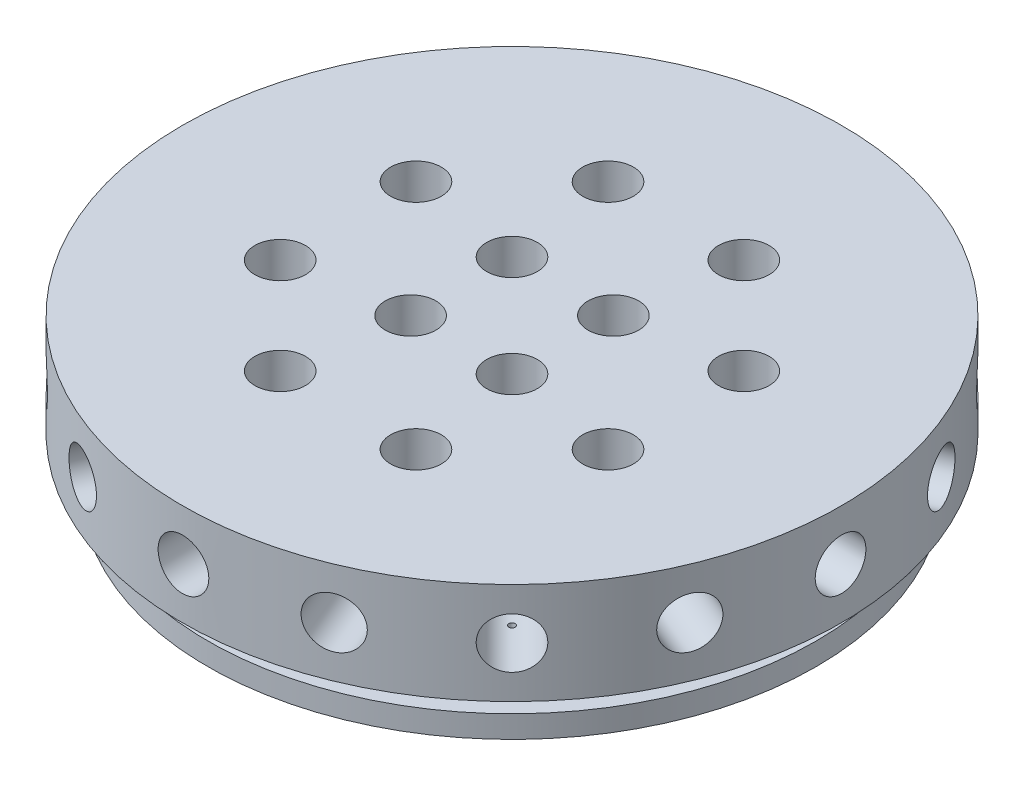
SolidWorks part; units mm, degrees
ref_plane "Front Plane" through (0, 0, 0) normal (0, 0, 1) x (1, 0, 0)
ref_plane "Top Plane" through (0, 0, 0) normal (0, 1, 0) x (1, 0, 0)
ref_plane "Right Plane" through (0, 0, 0) normal (1, 0, 0) x (0, 0, -1)
ref_axis "Axis1" through (0, -42.3, 0) along (0, 1, 0)
sketch "Sketch1" plane through (0, 0, 0) normal (0, 0, 1) x (1, 0, 0)
  line L0 (0, 0) -> (-38.1, 0)
  line L1 (-38.1, 0) -> (-38.1, 2.7877)
  line L2 (-38.1, 2.7877) -> (-36.068, 2.7877)
  line L3 (-36.068, 2.7877) -> (-36.068, 5.5563)
  line L4 (-36.068, 5.5563) -> (-38.1, 5.5563)
  line L5 (-38.1, 5.5563) -> (-38.1, 6.35)
  line L6 (-38.1, 6.35) -> (-41.275, 6.35)
  line L7 (-41.275, 6.35) -> (-41.275, 19.05)
  line L10 (-41.275, 19.05) -> (0, 19.05)
  line L11 (0, 19.05) -> (0, 0)
  dimension "D1" = 38.1
  dimension "D2" = 2.7686
  dimension "D3" = 12.7
  dimension "D4" = 0.7937
  dimension "D5" = 2.032
  dimension "D6" = 3.175
  dimension "D9" = 19.05
revolve "Revolve1" add sketch "Sketch1" angle 360 about L11
ref_plane "Plane1" through (41.275, 0, 0) normal (1, 0, 0) x (0, 0, -1)
hole_wizard "1/4 (0.25) Diameter Hole1" positions "Sketch12" profile "Sketch13" hole size "1/4" standard "ANSI Inch"
sketch "Sketch12" plane through (41.275, 0, 0) normal (1, 0, 0) x (0, 0, -1)
  point P0 (0, 12.7)
  dimension "D1" = 12.7
sketch "Sketch13" plane through (41.275, 12.7, 0) normal (0, 1, 0) x (0, 0, -1)
  line L0 (0, 0) -> (0, 14.6077)
  line L1 (0, 14.6077) -> (3.175, 12.7)
  line L2 (3.175, 12.7) -> (3.175, 0)
  line L5 (3.175, 0) -> (0, 0)
  line L10 (0, 14.6077) -> (-3.175, 12.7) construction
  line L11 (0, -6.35) -> (0, 107.95) construction
  dimension "Hole Dia." = 6.35
  dimension "Hole Depth" = 12.7
  dimension "Drill Angle" = 118
hole_wizard "3/16 (0.1875) Diameter Hole1" positions "Sketch14" profile "Sketch15" hole size "3/16" standard "ANSI Inch"
sketch "Sketch14" plane through (41.275, 0, 0) normal (1, 0, 0) x (0, 0, -1)
  point P0 (0, 12.7)
sketch "Sketch15" plane through (41.275, 12.7, 0) normal (0, 1, 0) x (0, 0, -1)
  line L0 (0, 0) -> (0, 26.8308)
  line L1 (0, 26.8308) -> (2.3812, 25.4)
  line L2 (2.3812, 25.4) -> (2.3812, 0)
  line L5 (2.3812, 0) -> (0, 0)
  line L10 (0, 26.8308) -> (-2.3813, 25.4) construction
  line L11 (0, -6.35) -> (0, 107.95) construction
  dimension "Hole Dia." = 4.7625
  dimension "Hole Depth" = 25.4
  dimension "Drill Angle" = 118
hole_wizard "1/8 (0.125) Diameter Hole1" positions "Sketch16" profile "Sketch17" hole size "1/8" standard "ANSI Inch"
sketch "Sketch16" plane through (41.275, 0, 0) normal (1, 0, 0) x (0, 0, -1)
  point P0 (0, 12.7)
sketch "Sketch17" plane through (41.275, 12.7, 0) normal (0, 1, 0) x (0, 0, -1)
  line L0 (0, 0) -> (0, 35.8789)
  line L1 (0, 35.8789) -> (1.5875, 34.925)
  line L2 (1.5875, 34.925) -> (1.5875, 0)
  line L5 (1.5875, 0) -> (0, 0)
  line L10 (0, 35.8789) -> (-1.5875, 34.925) construction
  line L11 (0, -6.35) -> (0, 107.95) construction
  dimension "Hole Dia." = 3.175
  dimension "Hole Depth" = 34.925
  dimension "Drill Angle" = 118
pattern_circular "CirPattern1" count 16 over 360 about axis through (0, -42.3, 0) along (0, 1, 0) of "1/4 (0.25) Diameter Hole1"
pattern_circular "CirPattern2" count 8 over 360 about axis through (0, -42.3, 0) along (0, 1, 0) of "3/16 (0.1875) Diameter Hole1"
pattern_circular "CirPattern3" count 4 over 360 about axis through (0, -42.3, 0) along (0, 1, 0) of "1/8 (0.125) Diameter Hole1"
ref_plane "Plane2" through (0, 19.05, 0) normal (0, 1, 0) x (1, 0, 0)
hole_wizard "inner large LOX holes" positions "Sketch19" profile "Sketch20" hole size "1/4" standard "ANSI Inch"
sketch "Sketch19" plane through (0, 19.05, 0) normal (0, 1, 0) x (1, 0, 0)
  line L2 (-6.35, 0) -> (0, 0) construction
  line L4 (-6.35, -6.35) -> (-6.35, 0) construction
  point P0 (-6.35, -6.35)
  point P17 (-5.8986, -6.5683)
  dimension "D1" = 6.35
  dimension "D2" = 6.35
sketch "Sketch20" plane through (-6.35, 19.05, 6.35) normal (1, 0, 0) x (0, 0, 1)
  line L0 (0, 0) -> (0, 14.6077)
  line L1 (0, 14.6077) -> (3.175, 12.7)
  line L2 (3.175, 12.7) -> (3.175, 0)
  line L5 (3.175, 0) -> (0, 0)
  line L10 (0, 14.6077) -> (-3.175, 12.7) construction
  line L11 (0, -6.35) -> (0, 107.95) construction
  dimension "Hole Dia." = 6.35
  dimension "Hole Depth" = 12.7
  dimension "Drill Angle" = 118
hole_wizard "outer large LOX hole" positions "Sketch21" profile "Sketch22" hole size "1/4" standard "ANSI Inch"
sketch "Sketch21" plane through (0, 19.05, 0) normal (0, 1, 0) x (1, 0, 0)
  line L0 (-20.5332, -8.5051) -> (0, 0) construction
  line L2 (0, 0) -> (-17.5003, 0) construction
  point P0 (-20.5332, -8.5051)
  point P15 (-24.1808, -10.016)
  dimension "D1" = 22.5
  dimension "D2" = 22.225
sketch "Sketch22" plane through (-20.5332, 19.05, 8.5051) normal (1, 0, 0) x (0, 0, 1)
  line L0 (0, 0) -> (0, 14.6077)
  line L1 (0, 14.6077) -> (3.175, 12.7)
  line L2 (3.175, 12.7) -> (3.175, 0)
  line L5 (3.175, 0) -> (0, 0)
  line L10 (0, 14.6077) -> (-3.175, 12.7) construction
  line L11 (0, -6.35) -> (0, 107.95) construction
  dimension "Hole Dia." = 6.35
  dimension "Hole Depth" = 12.7
  dimension "Drill Angle" = 118
pattern_circular "CirPattern4" count 4 over 360 about axis through (0, -42.3, 0) along (0, 1, 0) of "inner large LOX holes"
pattern_circular "CirPattern5" count 8 over 360 about axis through (0, -42.3, 0) along (0, 1, 0) of "outer large LOX hole"
ref_plane "Plane4" through (-34.925, 0, 0) normal (1, 0, 0) x (0, 0, -1)
ref_axis "Axis4" through (-34.925, 0, -45.4025) along (0, 0, 1)
ref_plane "Plane5" through (-0.2653, -3.0323, 0) normal (0.0872, 0.9962, 0) x (0, 0, 1)
ref_plane "Plane6" through (-0.4037, -4.6138, 0) normal (0.0872, 0.9962, 0) x (0, 0, 1)
hole_wizard "film cooling holes" positions "Sketch25" profile "Sketch26" hole size "1/32" standard "ANSI Inch"
sketch "Sketch25" plane through (-0.4037, -4.6138, 0) normal (0.0872, 0.9962, 0) x (0, 0, 1)
  line L0 (0, -34.7921) -> (0, 0) construction
  line L1 (-45.4025, -34.7921) -> (45.4025, -34.7921) construction
  point P0 (0, -34.7921)
  point P6 (0, -27.141)
  point P7 (0, -33.6297)
  point P8 (0, 0)
  point P9 (0, -35.267)
sketch "Sketch26" plane through (-35.0634, -1.5815, 0) normal (0, 0, 1) x (0.9962, -0.0872, 0)
  line L0 (0, 0) -> (0, 12.9385)
  line L1 (0, 12.9385) -> (0.3969, 12.7)
  line L2 (0.3969, 12.7) -> (0.3969, 0)
  line L5 (0.3969, 0) -> (0, 0)
  line L10 (0, 12.9385) -> (-0.3969, 12.7) construction
  line L11 (0, -6.35) -> (0, 107.95) construction
  dimension "Hole Dia." = 0.7937
  dimension "Hole Depth" = 12.7
  dimension "Drill Angle" = 118
pattern_circular "CirPattern6" count 16 over 360 about axis through (0, -42.3, 0) along (0, 1, 0) of "film cooling holes"
hole_wizard "1/32 (0.03125) Diameter Hole3" positions "Sketch27" profile "Sketch28" hole size "1/32" standard "ANSI Inch"
sketch "Sketch27" plane through (0, 0, 0) normal (0, 1, 0) x (1, 0, 0)
  point P0 (-6.35, 0)
  point P3 (-6.5364, 0.8154)
  dimension "D1" = 6.35
sketch "Sketch28" plane through (-6.35, 0, 0) normal (1, 0, 0) x (0, 0, -1)
  line L0 (0, 0) -> (0, 12.9385)
  line L1 (0, 12.9385) -> (0.3969, 12.7)
  line L2 (0.3969, 12.7) -> (0.3969, 0)
  line L5 (0.3969, 0) -> (0, 0)
  line L10 (0, 12.9385) -> (-0.3969, 12.7) construction
  line L11 (0, -6.35) -> (0, 107.95) construction
  dimension "Hole Dia." = 0.7937
  dimension "Hole Depth" = 12.7
  dimension "Drill Angle" = 118
ref_axis "Axis2" through (0, 19.05, -45.4025) along (0, 0, 1)
ref_axis "Axis3" through (45.4025, 19.05, 0) along (-1, 0, 0)
